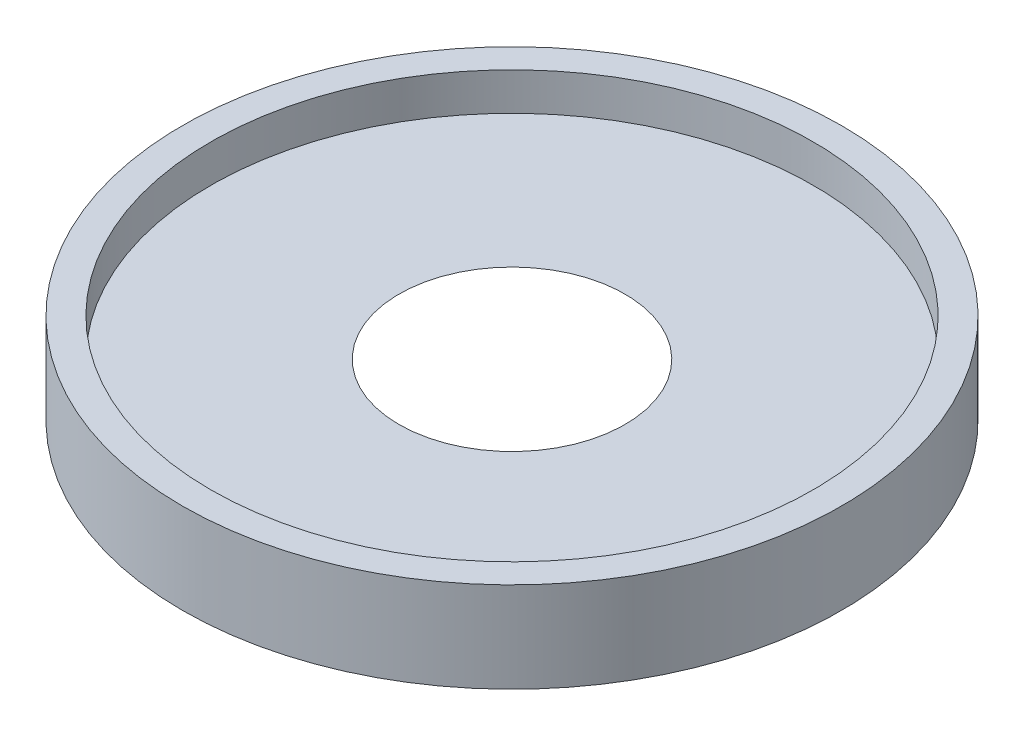
SolidWorks part; units mm, degrees
ref_plane "Front Plane" through (0, 0, 0) normal (0, 0, 1) x (1, 0, 0)
ref_plane "Top Plane" through (0, 0, 0) normal (0, 1, 0) x (1, 0, 0)
ref_plane "Right Plane" through (0, 0, 0) normal (1, 0, 0) x (0, 0, -1)
sketch "Sketch2" plane through (0, 0, 0) normal (0, 1, 0) x (1, 0, 0)
  circle A0 centre (0, 0) radius 11.1125
extrude "Boss-Extrude1" add sketch "Sketch2" along normal blind 3.048
sketch "Sketch3" plane through (0, 3.048, 0) normal (0, 1, 0) x (1, 0, 0)
  circle A0 centre (0, 0) radius 10.16
  dimension "D1" = 20.32
extrude "Cut-Extrude1" cut sketch "Sketch3" against normal blind 1.27
sketch "Sketch4" plane through (0, 0, 0) normal (0, -1, 0) x (-1, 0, 0)
  circle A0 centre (0, 0) radius 3.81
extrude "Cut-Extrude2" cut sketch "Sketch4" against normal blind 2.54
fillet "Fillet1" radius 10.16 1 edges at (0, 0, -3.81)
